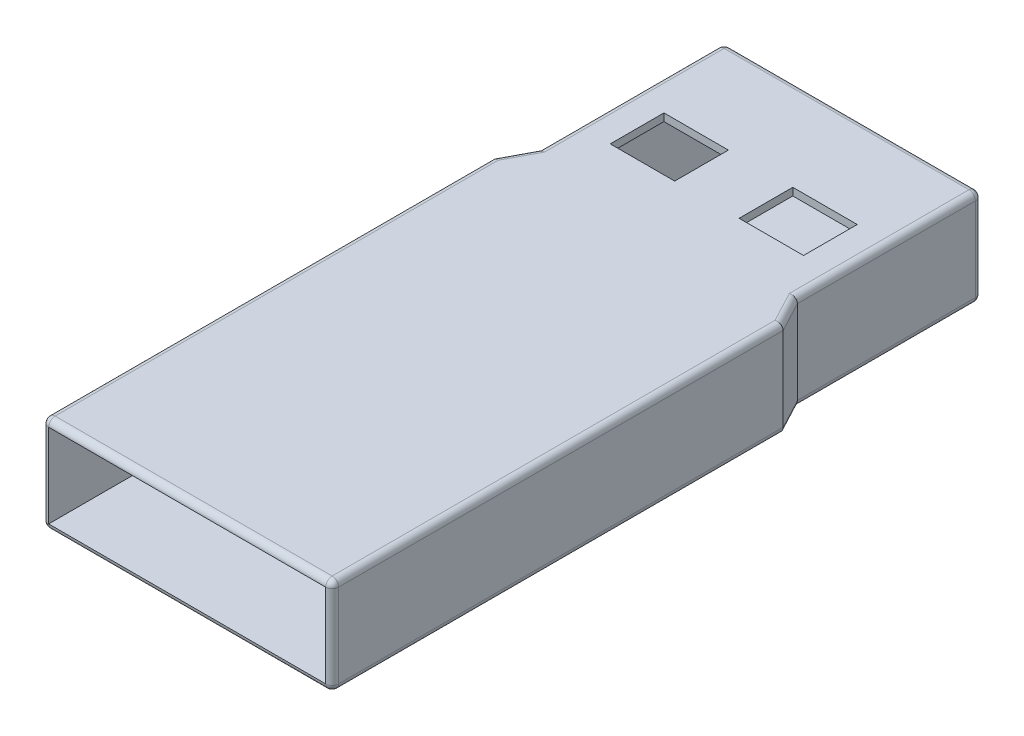
SolidWorks part; units mm, degrees
ref_plane "Front Plane" through (0, 0, 0) normal (0, 0, 1) x (1, 0, 0)
ref_plane "Top Plane" through (0, 0, 0) normal (0, 1, 0) x (1, 0, 0)
ref_plane "Right Plane" through (0, 0, 0) normal (1, 0, 0) x (0, 0, -1)
sketch "Sketch1" plane through (0, 0, 0) normal (0, 1, 0) x (1, 0, 0)
  line L0 (-6.75, -7.0476) -> (6.75, -7.0476)
  line L1 (6.75, -7.0476) -> (6.75, 13.9524)
  line L3 (6, 15.3657) -> (6, 23.9524)
  line L4 (6, 23.9524) -> (-6, 23.9524)
  line L5 (-6, 23.9524) -> (-6, 15.3657)
  line L7 (-6.75, 13.9524) -> (-6.75, -7.0476)
  line L8 (0, 0) -> (0, 28.0625) construction
  line L9 (-6.75, 13.9524) -> (-6, 15.3657)
  line L10 (6.75, 13.9524) -> (6, 15.3657)
  dimension "D2" = 21
  dimension "D3" = 13.5
  dimension "D4" = 12
  dimension "D5" = 1.6
  dimension "D6" = 1.6
extrude "Boss-Extrude1" add sketch "Sketch1" along normal blind 4.5
fillet "Fillet1" radius 0.3 16 edges at (6.375, 0, -14.659) (6, 0, -19.659) (0, 0, -23.9524) (-6, 0, -19.659) (-6.375, 0, -14.659) (-6.75, 0, -3.4524) (0, 0, 7.0476) (6.75, 0, -3.4524) (0, 4.5, 7.0476) (-6.75, 4.5, -3.4524) (-6.375, 4.5, -14.659) (-6, 4.5, -19.659) (0, 4.5, -23.9524) (6, 4.5, -19.659) (6.375, 4.5, -14.659) (6.75, 4.5, -3.4524)
fillet "Fillet2" radius 0.3 12 edges at (-5.9121, 4.4121, -23.8645) (-5.9121, 0.0879, -23.8645) (5.9121, 4.4121, -23.8645) (5.9121, 0.0879, -23.8645) (6.6621, 4.4121, 6.9598) (6.6621, 0.0879, 6.9598) (-6.6621, 4.4121, 6.9598) (-6.6621, 0.0879, 6.9598) (-6, 2.25, -23.9524) (6, 2.25, -23.9524) (6.75, 2.25, 7.0476) (-6.75, 2.25, 7.0476)
shell "Shell3" thickness 0.35 removed face at (0, 2.25, -23.9524)
sketch "Sketch3" plane through (0, 0, 7.0476) normal (0, 0, 1) x (1, 0, 0)
  line L1 (-6.45, 4.2) -> (6.45, 4.2)
  line L2 (-6.45, 4.2) -> (-6.45, 0.3)
  line L3 (-6.45, 0.3) -> (6.45, 0.3)
  line L4 (6.45, 4.2) -> (6.45, 0.3)
extrude "Cut-Extrude1" cut sketch "Sketch3" against normal up to vertex (21 mm away) up to point (6.75, 4.2, -13.9524)
sketch "Sketch4" plane through (0, 4.5, 0) normal (0, 1, 0) x (1, 0, 0)
  line L0 (-5.7, 15.291) -> (5.7, 15.291)
  line L1 (1.5, 19.6524) -> (4.5, 19.6524)
  line L2 (1.5, 19.6524) -> (1.5, 17.1524)
  line L3 (1.5, 17.1524) -> (4.5, 17.1524)
  line L4 (4.5, 19.6524) -> (4.5, 17.1524)
  line L5 (-4.5, 19.6524) -> (-1.5, 19.6524)
  line L6 (-4.5, 19.6524) -> (-4.5, 17.1524)
  line L7 (-4.5, 17.1524) -> (-1.5, 17.1524)
  line L8 (-1.5, 19.6524) -> (-1.5, 17.1524)
  line L9 (0, 24.588) -> (0, 15.4172) construction
  dimension "D1" = 3
  dimension "D2" = 2.5
  dimension "D3" = 3
  dimension "D4" = 2.5
  dimension "D5" = 4
  dimension "D6" = 1.5
extrude "Cut-Extrude2" cut sketch "Sketch4" against normal up to next contours L4 L1 L2 L3 | L8 L5 L6 L7 region at (3, 4.5, -18.4024) region at (-3, 4.5, -18.4024)
